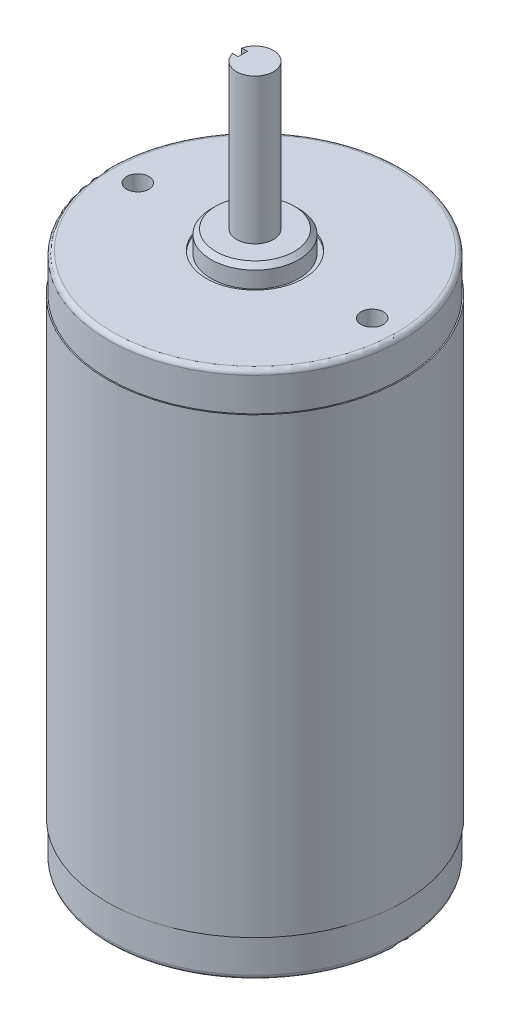
SolidWorks part; units mm, degrees
ref_plane "Front Plane" through (0, 0, 0) normal (0, 0, 1) x (1, 0, 0)
ref_plane "Top Plane" through (0, 0, 0) normal (0, 1, 0) x (1, 0, 0)
ref_plane "Right Plane" through (0, 0, 0) normal (1, 0, 0) x (0, 0, -1)
sketch "Sketch1" plane through (0, 0, 0) normal (0, 0, 1) x (1, 0, 0)
  line L0 (0, 0) -> (0, 181.9697) construction
  line L1 (10.5283, 119.3673) -> (10.5283, 118.8593)
  line L2 (10.5283, 118.8593) -> (9.525, 118.8593)
  line L3 (9.525, 118.8593) -> (9.525, 123.4313)
  line L4 (0, 0) -> (0, 154.9314)
  line L5 (9.525, 123.4313) -> (4, 123.4313)
  line L6 (4, 123.4313) -> (4, 154.9314)
  line L7 (4, 154.9314) -> (0, 154.9314)
  line L8 (32.004, 62.0649) -> (0, 62.0649) construction
  line L28 (0, 0) -> (15.0368, 0)
  line L29 (15.0368, 0) -> (15.0368, 4.7625)
  line L30 (15.0368, 4.7625) -> (31.75, 4.7625)
  line L31 (31.75, 4.7625) -> (31.75, 12.9921)
  line L32 (31.75, 12.9921) -> (32.004, 12.9921)
  line L33 (32.004, 12.9921) -> (32.004, 111.1377)
  line L34 (32.004, 111.1377) -> (31.75, 111.1377)
  line L35 (31.75, 111.1377) -> (31.75, 119.3673)
  line L41 (31.75, 119.3673) -> (10.5283, 119.3673)
  dimension "D4" = 64.008
  dimension "D13" = 62.0649
  dimension "D1" = 8
  dimension "D2" = 154.9314
  dimension "D3" = 30.0736
  dimension "D5" = 19.05
  dimension "D6" = 21.0566
  dimension "D7" = 0.508
  dimension "D8" = 4.064
  dimension "D9" = 0.254
  dimension "D10" = 63.5
  dimension "D11" = 114.6048
  dimension "D12" = 4.7625
  dimension "D14" = 98.1456
revolve "Revolve1" add sketch "Sketch1" angle 360 about L4
chamfer "Chamfer1" distance 1.0162 angle 45 1 edges at (0, 123.4313, -9.525)
fillet "Fillet1" radius 1 3 edges at (0, 119.3673, -31.75) (0, 4.7625, -31.75) (0, 0, -15.0368)
hole_wizard "A (0.234) Diameter Hole2" positions "Sketch3" profile "Sketch4" hole size "A" standard "Ansi (в дюймах)"
sketch "Sketch3" plane through (0, 119.3673, 0) normal (0, 1, 0) x (-1, 0, 0)
  line L0 (0, 0) -> (0, -20.2399) construction
  line L2 (23.6801, 0) -> (-25.6264, 0) construction
  point P0 (25.4, 0)
  point P1 (-25.4, 0)
  dimension "D1" = 25.4
sketch "Sketch4" plane through (-25.4, 119.3673, 0) normal (1, 0, 0) x (0, 0, 1)
  line L0 (0, 0) -> (0, 14.9119)
  line L1 (0, 14.9119) -> (2.413, 13.462)
  line L2 (2.413, 13.462) -> (2.413, 0)
  line L5 (2.413, 0) -> (0, 0)
  line L10 (0, 14.9119) -> (-2.413, 13.462) construction
  line L11 (0, -6.35) -> (0, 107.95) construction
  dimension "Диаметр отверстия" = 4.826
  dimension "Глубина отверстия" = 13.462
  dimension "Угол заточки сверла" = 118
sketch "Sketch5" plane through (0, 154.9314, 0) normal (0, 1, 0) x (1, 0, 0)
  line L0 (0, 0) -> (-5.7838, 0) construction
  line L2 (-4, -1) -> (-2.65, -1)
  line L3 (-4, -1) -> (-4, 1)
  line L4 (-4, 1) -> (-2.65, 1)
  line L5 (-2.65, -1) -> (-2.65, 1)
  circle A0 centre (0, 0) radius 4 construction
  dimension "D1" = 1.35
  dimension "D2" = 2
extrude "Extrude1" cut sketch "Sketch5" against normal blind 29.8
fillet "Fillet2" radius 12.7 1 edges at (-2.65, 125.1314, 0)
sketch "Sketch6" plane through (0, 4.7625, 0) normal (0, -1, 0) x (1, 0, 0)
  line L0 (0, 0) -> (-35.7085, 0) construction
  line L1 (0, 0) -> (18.6071, -11.2074) construction
  circle A0 centre (18.6071, -11.2074) radius 4.3178
  dimension "D1" = 8.6357
  dimension "D2" = 148.939
  dimension "D3" = 21.7216
extrude "Extrude2" add sketch "Sketch6" along normal blind 2.25 draft 45
ref_axis "Axis1" through (0, 111.1377, 0) along (0, -1, 0)
pattern_circular "CirPattern1" count 2 every 27.877 about axis through (0, 111.1377, 0) along (0, -1, 0) of "Extrude2" reverse direction yes
